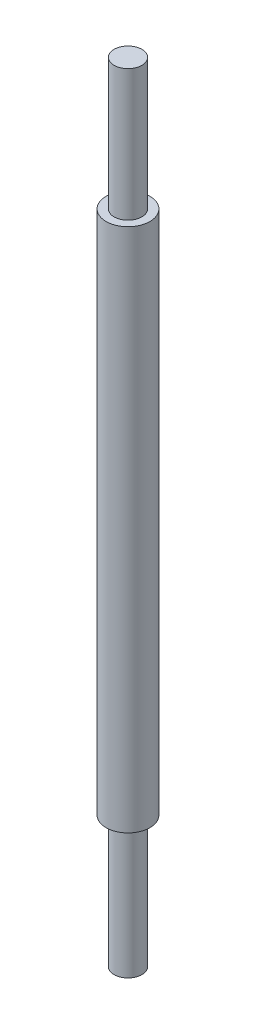
SolidWorks part; units mm, degrees
ref_plane "Front Plane" through (0, 0, 0) normal (0, 0, 1) x (1, 0, 0)
ref_plane "Top Plane" through (0, 0, 0) normal (0, 1, 0) x (1, 0, 0)
ref_plane "Right Plane" through (0, 0, 0) normal (1, 0, 0) x (0, 0, -1)
sketch "Sketch1" plane through (0, 0, 0) normal (0, 1, 0) x (1, 0, 0)
  circle A0 centre (0, 0) radius 5
  circle A1 centre (0, 0) radius 3.175
extrude "Boss-Extrude2" add sketch "Sketch1" along normal mid plane 180 contours A1
extrude "Boss-Extrude3" add sketch "Sketch1<4>" along normal mid plane 120
sketch "Sketch1<4>" plane through (0, 0, 0) normal (0, 1, 0) x (1, 0, 0) same geometry as "Sketch1"
